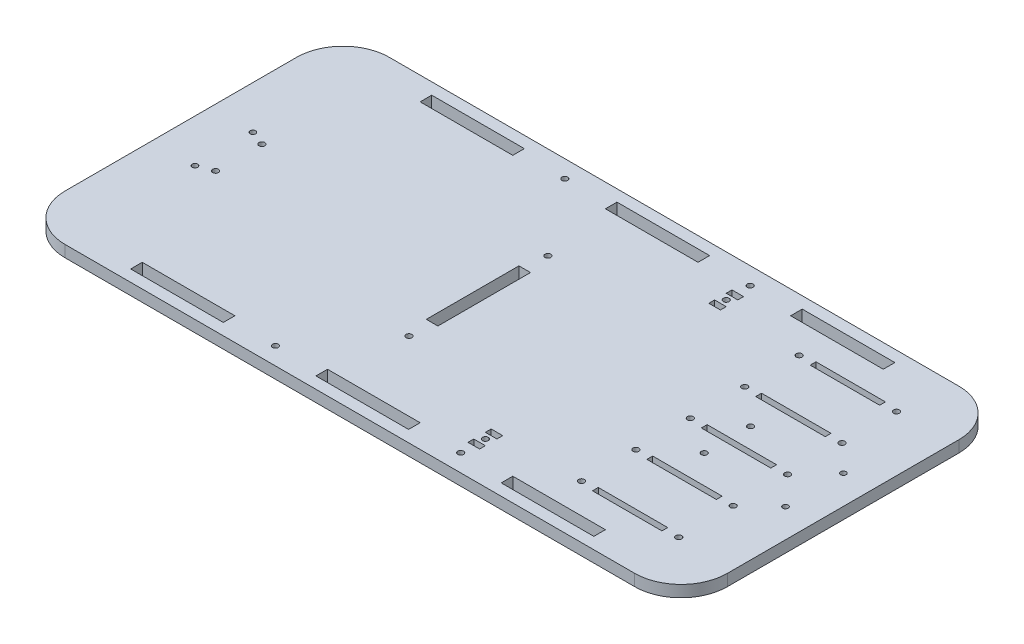
SolidWorks part; units mm, degrees
ref_plane "Front Plane" through (0, 0, 0) normal (0, 0, 1) x (1, 0, 0)
ref_plane "Top Plane" through (0, 0, 0) normal (0, 1, 0) x (1, 0, 0)
ref_plane "Right Plane" through (0, 0, 0) normal (1, 0, 0) x (0, 0, -1)
sketch "Sketch3" plane through (0, 0, 0) normal (0, 1, 0) x (1, 0, 0)
  line L1 (-156.21, -88.9) -> (156.21, -88.9)
  line L2 (-181.61, -63.5) -> (-181.61, 63.5)
  line L3 (-156.21, 88.9) -> (156.21, 88.9)
  line L4 (181.61, -63.5) -> (181.61, 63.5)
  line L5 (-181.61, -88.9) -> (181.61, 88.9) construction
  line L6 (-181.61, 88.9) -> (181.61, -88.9) construction
  arc A0 (156.21, -88.9) -> (181.61, -63.5) centre (156.21, -63.5) ccw
  arc A1 (156.21, 88.9) -> (181.61, 63.5) centre (156.21, 63.5) cw
  arc A2 (-156.21, -88.9) -> (-181.61, -63.5) centre (-156.21, -63.5) cw
  arc A3 (-181.61, 63.5) -> (-156.21, 88.9) centre (-156.21, 63.5) cw
  point P0 (0, 0)
  dimension "D3" = 25.4
  dimension "D1" = 177.8
  dimension "D2" = 363.22
extrude "BaseExtrude" add sketch "Sketch3" against normal blind 6.35
sketch "Sketch6" plane through (0, 0, 0) normal (0, 1, 0) x (1, 0, 0)
  line L0 (-181.61, 0) -> (181.61, 0) construction
  line L1 (-181.61, 63.5) -> (-181.61, -63.5) construction
  line L2 (181.61, -63.5) -> (181.61, 63.5) construction
  line L3 (0, -88.9) -> (0, 88.9) construction
  line L4 (-156.21, -88.9) -> (156.21, -88.9) construction
  line L5 (156.21, 88.9) -> (-156.21, 88.9) construction
  line L6 (3.937, 0) -> (3.937, 19.6413) construction
  circle A0 centre (-157.988, 15.875) radius 1.5
  circle A1 centre (-157.988, -15.875) radius 1.5
  circle A2 centre (165.862, -15.875) radius 1.5
  circle A3 centre (165.862, 15.875) radius 1.5
  dimension "D2" = 3
  dimension "D1" = 23.622
  dimension "D3" = 15.875
  dimension "D4" = 161.925
extrude "MainMountCut" cut sketch "Sketch6" against normal up to surface (6.35 mm away) up to face at (0, -6.35, 0)
sketch "Sketch7" plane through (0, 0, 0) normal (0, 1, 0) x (1, 0, 0)
  line L0 (76.6233, 79.375) -> (25.8233, 79.375) construction
  line L1 (127.4233, -82.55) -> (76.6233, -82.55)
  line L2 (127.4233, -82.55) -> (127.4233, -76.2)
  line L3 (127.4233, -76.2) -> (76.6233, -76.2)
  line L4 (76.6233, -82.55) -> (76.6233, -76.2)
  line L5 (25.8233, -82.55) -> (-24.9767, -82.55)
  line L6 (25.8233, -82.55) -> (25.8233, -76.2)
  line L7 (25.8233, -76.2) -> (-24.9767, -76.2)
  line L8 (-24.9767, -82.55) -> (-24.9767, -76.2)
  line L9 (-75.7767, -82.55) -> (-126.5767, -82.55)
  line L10 (-75.7767, -82.55) -> (-75.7767, -76.2)
  line L11 (-75.7767, -76.2) -> (-126.5767, -76.2)
  line L12 (-126.5767, -82.55) -> (-126.5767, -76.2)
  line L13 (127.4233, 76.2) -> (76.6233, 76.2)
  line L14 (127.4233, 76.2) -> (127.4233, 82.55)
  line L15 (127.4233, 82.55) -> (76.6233, 82.55)
  line L16 (76.6233, 76.2) -> (76.6233, 82.55)
  line L17 (25.8233, 76.2) -> (-24.9767, 76.2)
  line L18 (25.8233, 76.2) -> (25.8233, 82.55)
  line L19 (25.8233, 82.55) -> (-24.9767, 82.55)
  line L20 (-24.9767, 76.2) -> (-24.9767, 82.55)
  line L21 (-75.7767, 76.2) -> (-126.5767, 76.2)
  line L22 (-75.7767, 76.2) -> (-75.7767, 82.55)
  line L23 (-75.7767, 82.55) -> (-126.5767, 82.55)
  line L24 (-126.5767, 76.2) -> (-126.5767, 82.55)
  line L25 (-24.9767, 79.375) -> (-75.7767, 79.375) construction
  line L26 (-75.7767, -79.375) -> (-24.9767, -79.375) construction
  line L27 (76.6233, -79.375) -> (25.8233, -79.375) construction
  line L28 (181.61, -63.5) -> (181.61, 63.5) construction
  line L32 (-156.21, -88.9) -> (156.21, -88.9) construction
  line L35 (156.21, 88.9) -> (-156.21, 88.9) construction
  circle A0 centre (51.2233, 79.375) radius 1.6
  circle A1 centre (-50.3767, 79.375) radius 1.6
  circle A2 centre (-50.3767, -79.375) radius 1.6
  circle A3 centre (51.2233, -79.375) radius 1.6
  dimension "D5" = 3.2
  dimension "D1" = 50.8
  dimension "D2" = 6.35
  dimension "D3" = 6.35
  dimension "D4" = 6.35
  dimension "D6" = 54.1867
extrude "WallCut" cut sketch "Sketch7" against normal through all
sketch "Sketch8" plane through (0, 0, 0) normal (0, 1, 0) x (1, 0, 0)
  line L0 (124.46, -58.1025) -> (124.46, -31.4325) construction
  line L1 (143.51, -61.2775) -> (105.41, -61.2775)
  line L2 (143.51, -61.2775) -> (143.51, -58.1025)
  line L3 (143.51, -58.1025) -> (105.41, -58.1025)
  line L4 (105.41, -61.2775) -> (105.41, -58.1025)
  line L5 (143.51, -31.4325) -> (105.41, -31.4325)
  line L6 (143.51, -31.4325) -> (143.51, -28.2575)
  line L7 (143.51, -28.2575) -> (105.41, -28.2575)
  line L8 (105.41, -31.4325) -> (105.41, -28.2575)
  line L9 (143.51, -1.5875) -> (105.41, -1.5875)
  line L10 (143.51, -1.5875) -> (143.51, 1.5875)
  line L11 (143.51, 1.5875) -> (105.41, 1.5875)
  line L12 (105.41, -1.5875) -> (105.41, 1.5875)
  line L13 (143.51, 28.2575) -> (105.41, 28.2575)
  line L14 (143.51, 28.2575) -> (143.51, 31.4325)
  line L15 (143.51, 31.4325) -> (105.41, 31.4325)
  line L16 (105.41, 28.2575) -> (105.41, 31.4325)
  line L17 (143.51, 58.1025) -> (105.41, 58.1025)
  line L18 (143.51, 58.1025) -> (143.51, 61.2775)
  line L19 (143.51, 61.2775) -> (105.41, 61.2775)
  line L20 (105.41, 58.1025) -> (105.41, 61.2775)
  line L21 (124.46, -28.2575) -> (124.46, -1.5875) construction
  line L22 (124.46, -61.2775) -> (124.46, -76.2) construction
  line L23 (124.46, 1.5875) -> (124.46, 28.2575) construction
  line L24 (124.46, 31.4325) -> (124.46, 58.1025) construction
  line L25 (127.4233, -76.2) -> (76.6233, -76.2) construction
  line L26 (124.46, 61.2775) -> (124.46, 76.2) construction
  line L27 (76.6233, 76.2) -> (127.4233, 76.2) construction
  line L28 (181.61, -63.5) -> (181.61, 63.5) construction
  line L29 (143.51, -59.69) -> (151.13, -59.69) construction
  line L30 (151.13, -59.69) -> (151.13, 59.69) construction
  line L31 (151.13, 59.69) -> (143.51, 59.69) construction
  line L32 (143.51, 29.845) -> (151.13, 29.845) construction
  line L33 (143.51, 0) -> (151.13, 0) construction
  line L34 (143.51, -29.845) -> (151.13, -29.845) construction
  line L35 (105.41, -59.69) -> (97.79, -59.69) construction
  line L36 (97.79, -59.69) -> (97.79, 59.69) construction
  line L37 (97.79, 59.69) -> (105.41, 59.69) construction
  line L38 (105.41, 29.845) -> (97.79, 29.845) construction
  line L39 (105.41, 0) -> (97.79, 0) construction
  line L40 (105.41, -29.845) -> (97.79, -29.845) construction
  circle A0 centre (151.13, -59.69) radius 1.6
  circle A1 centre (151.13, -29.845) radius 1.6
  circle A2 centre (151.13, 0) radius 1.6
  circle A3 centre (151.13, 29.845) radius 1.6
  circle A4 centre (151.13, 59.69) radius 1.6
  circle A5 centre (97.79, 59.69) radius 1.6
  circle A6 centre (97.79, 29.845) radius 1.6
  circle A7 centre (97.79, 0) radius 1.6
  circle A8 centre (97.79, -29.845) radius 1.6
  circle A9 centre (97.79, -59.69) radius 1.6
  dimension "D6" = 3.2
  dimension "D1" = 3.175
  dimension "D2" = 26.67
  dimension "D3" = 38.1
  dimension "D4" = 57.15
  dimension "D5" = 7.62
extrude "WireMountCut" cut sketch "Sketch8" against normal through all
sketch "Sketch9" plane through (0, 0, 0) normal (0, 1, 0) x (1, 0, 0)
  line L0 (118.11, -12.7) -> (118.11, 12.7) construction
  line L1 (-149.86, -12.7) -> (-149.86, 12.7) construction
  line L2 (-149.86, 12.7) -> (118.11, 12.7) construction
  line L3 (118.11, -12.7) -> (-149.86, -12.7) construction
  line L4 (118.11, -12.7) -> (118.11, -88.9) construction
  line L5 (-156.21, -88.9) -> (156.21, -88.9) construction
  line L6 (118.11, 12.7) -> (118.11, 88.9) construction
  line L7 (156.21, 88.9) -> (-156.21, 88.9) construction
  line L8 (-181.61, 63.5) -> (-181.61, -63.5) construction
  line L9 (181.61, -63.5) -> (181.61, 63.5) construction
  circle A0 centre (118.11, 12.7) radius 1.6
  circle A1 centre (118.11, -12.7) radius 1.6
  circle A2 centre (-149.86, -12.7) radius 1.6
  circle A3 centre (-149.86, 12.7) radius 1.6
  dimension "D1" = 3.2
  dimension "D2" = 76.2
  dimension "D3" = 31.75
  dimension "D4" = 63.5
extrude "Cut-Extrude3" cut sketch "Sketch9" against normal through all
sketch "Sketch11" plane through (0, 0, 0) normal (0, 1, 0) x (1, 0, 0)
  line L0 (54.61, 72.39) -> (48.26, 72.39)
  line L1 (54.61, -69.215) -> (54.61, -62.865) construction
  line L2 (54.61, 59.69) -> (48.26, 59.69)
  line L3 (54.61, -72.39) -> (54.61, -69.215)
  line L4 (54.61, -69.215) -> (48.26, -69.215)
  line L5 (181.61, 0) -> (-181.61, 0) construction
  line L6 (181.61, -63.5) -> (181.61, 63.5) construction
  line L7 (-181.61, 63.5) -> (-181.61, -63.5) construction
  line L8 (51.435, 66.04) -> (51.435, 62.865) construction
  line L9 (-15.24, -25.4) -> (-21.59, -25.4)
  line L10 (-15.24, -25.4) -> (-15.24, 25.4)
  line L11 (-15.24, 25.4) -> (-21.59, 25.4)
  line L12 (-21.59, -25.4) -> (-21.59, 25.4)
  line L13 (48.26, -72.39) -> (48.26, -69.215)
  line L14 (54.61, -62.865) -> (48.26, -62.865)
  line L15 (54.61, -62.865) -> (54.61, -59.69)
  line L17 (48.26, -62.865) -> (48.26, -59.69)
  line L18 (51.435, -69.215) -> (51.435, -66.04) construction
  line L19 (48.26, -69.215) -> (48.26, -62.865) construction
  line L20 (51.435, -66.04) -> (51.435, -62.865) construction
  line L22 (48.26, 69.215) -> (48.26, 62.865) construction
  line L23 (51.435, 69.215) -> (51.435, 66.04) construction
  line L24 (54.61, 69.215) -> (54.61, 62.865) construction
  line L25 (48.26, 62.865) -> (48.26, 59.69)
  line L27 (54.61, 62.865) -> (54.61, 59.69)
  line L28 (54.61, 62.865) -> (48.26, 62.865)
  line L29 (48.26, 72.39) -> (48.26, 69.215)
  line L30 (54.61, 69.215) -> (48.26, 69.215)
  line L31 (54.61, 72.39) -> (54.61, 69.215)
  line L33 (51.435, -66.04) -> (51.435, -62.865) construction
  line L34 (-18.415, -25.4) -> (-18.415, -38.1) construction
  line L35 (-18.415, 25.4) -> (-18.415, 38.1) construction
  line L36 (54.61, -72.39) -> (48.26, -72.39)
  line L37 (54.61, -59.69) -> (48.26, -59.69)
  circle A0 centre (51.435, -66.04) radius 1.6
  circle A1 centre (51.435, 66.04) radius 1.6
  circle A2 centre (-18.415, -38.1) radius 1.6
  circle A3 centre (-18.415, 38.1) radius 1.6
  point P45 (-15.24, 0)
  dimension "D4" = 50.8
  dimension "D2" = 3.2
  dimension "D9" = 3.2
  dimension "D1" = 12.7
  dimension "D6" = 63.5
  dimension "D7" = 50.8
  dimension "D8" = 12.7
extrude "Cut-Extrude4" cut sketch "Sketch11" against normal through all
